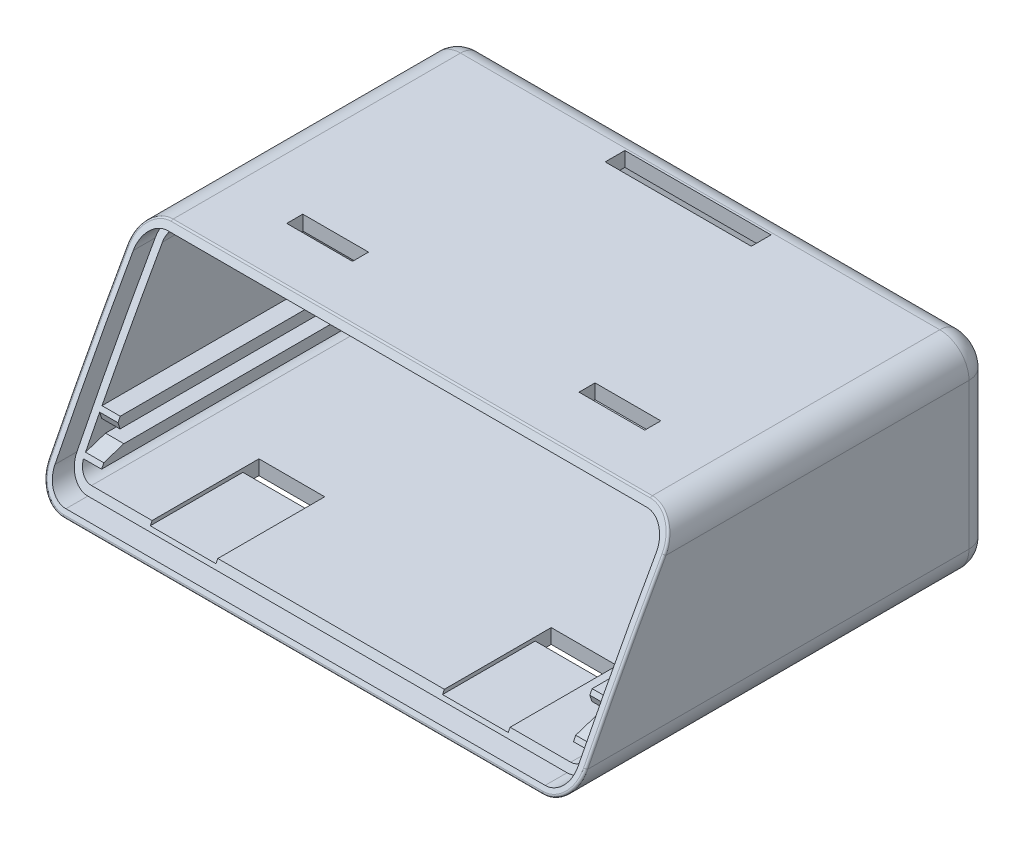
SolidWorks part; units mm, degrees
ref_plane "Front Plane" through (0, 0, 0) normal (0, 0, 1) x (1, 0, 0)
ref_plane "Top Plane" through (0, 0, 0) normal (0, 1, 0) x (1, 0, 0)
ref_plane "Right Plane" through (0, 0, 0) normal (1, 0, 0) x (0, 0, -1)
sketch "Sketch1" plane through (0, 0, 0) normal (0, 1, 0) x (1, 0, 0)
  line L1 (-36.79, -28.75) -> (36.79, -28.75)
  line L2 (-36.79, -28.75) -> (-36.79, 28.75)
  line L3 (-36.79, 28.75) -> (36.79, 28.75)
  line L4 (36.79, -28.75) -> (36.79, 28.75)
  line L5 (-36.79, -28.75) -> (36.79, 28.75) construction
  line L6 (-36.79, 28.75) -> (36.79, -28.75) construction
  point P0 (0, 0)
  dimension "D1" = 57.5
  dimension "D2" = 73.58
extrude "Boss-Extrude1" add sketch "Sketch1" along normal blind 28
fillet "Fillet1" radius 4 4 edges at (36.79, 28, 0) (36.79, 0, 0) (-36.79, 0, 0) (-36.79, 28, 0)
shell "Shell1" thickness 2
sketch "Sketch2" plane through (-36.79, 0, 0) normal (-1, 0, 0) x (0, 0, 1)
  line L0 (-28.75, 28) -> (28.75, 28) construction
  line L1 (13.75, 28) -> (28.75, 28)
  line L2 (28.75, 28) -> (28.75, 0)
  arc A0 (28.75, 0) -> (13.75, 28) centre (-397.2189, -210.1797) ccw
  dimension "D1" = 15
  dimension "D2" = 475
extrude "Cut-Extrude1" cut sketch "Sketch2" against normal through all
sketch "Sketch3" plane through (0, 0, -28.75) normal (0, 0, -1) x (-1, 0, 0)
  line L0 (-7.15, 18.7) -> (7.15, 18.7)
  line L1 (-6.95, 18.5) -> (6.95, 18.5) construction
  line L2 (-6.95, 18.5) -> (-6.95, 2.2) construction
  line L3 (-6.95, 2.2) -> (6.95, 2.2) construction
  line L4 (6.95, 18.5) -> (6.95, 2.2) construction
  line L5 (7.15, 18.7) -> (7.15, 2)
  line L6 (-7.15, 2) -> (7.15, 2)
  line L7 (-7.15, 18.7) -> (-7.15, 2)
  line L8 (27.25, 17.2) -> (38.3, 17.2)
  line L9 (27.45, 17) -> (38.1, 17) construction
  line L10 (27.45, 17) -> (27.45, 3.35) construction
  line L11 (27.45, 3.35) -> (38.1, 3.35) construction
  line L12 (38.1, 17) -> (38.1, 3.35) construction
  line L13 (38.3, 17.2) -> (38.3, 3.15)
  line L14 (27.25, 3.15) -> (38.3, 3.15)
  line L15 (27.25, 17.2) -> (27.25, 3.15)
  dimension "D1" = 0.2
  dimension "D2" = 0.2
fillet "Fillet2" radius 3 8 edges at (35.6184, 26.8284, -28.75) (36.79, 14, -28.75) (35.6184, 1.1716, -28.75) (0, 0, -28.75) (-35.6184, 1.1716, -28.75) (-36.79, 14, -28.75) (-35.6184, 26.8284, -28.75) (0, 28, -28.75)
sketch "Sketch4" plane through (0, 0, -26.75) normal (0, 0, 1) x (1, 0, 0)
  line L0 (32.79, 27) -> (-32.79, 27)
  line L1 (-35.79, 24) -> (-35.79, 4)
  line L2 (-32.79, 1) -> (32.79, 1)
  line L3 (35.79, 4) -> (35.79, 24)
  line L4 (32.79, 26) -> (-32.79, 26)
  line L5 (-34.79, 24) -> (-34.79, 4)
  line L6 (-32.79, 2) -> (32.79, 2)
  line L7 (34.79, 4) -> (34.79, 24)
  line L8 (32.79, 26) -> (-32.79, 26)
  line L9 (-34.79, 24) -> (-34.79, 4)
  line L10 (-32.79, 2) -> (32.79, 2)
  line L11 (34.79, 4) -> (34.79, 24)
  arc A0 (-32.79, 27) -> (-35.79, 24) centre (-32.79, 24) ccw
  arc A1 (-35.79, 4) -> (-32.79, 1) centre (-32.79, 4) ccw
  arc A2 (32.79, 1) -> (35.79, 4) centre (32.79, 4) ccw
  arc A3 (35.79, 24) -> (32.79, 27) centre (32.79, 24) ccw
  arc A4 (-32.79, 26) -> (-34.79, 24) centre (-32.79, 24) ccw
  arc A5 (-34.79, 4) -> (-32.79, 2) centre (-32.79, 4) ccw
  arc A6 (32.79, 2) -> (34.79, 4) centre (32.79, 4) ccw
  arc A7 (34.79, 24) -> (32.79, 26) centre (32.79, 24) ccw
  arc A8 (-32.79, 26) -> (-34.79, 24) centre (-32.79, 24) ccw
  arc A9 (-34.79, 4) -> (-32.79, 2) centre (-32.79, 4) ccw
  arc A10 (32.79, 2) -> (34.79, 4) centre (32.79, 4) ccw
  arc A11 (34.79, 24) -> (32.79, 26) centre (32.79, 24) ccw
  dimension "D1" = 0
  dimension "D2" = 1
extrude "Cut-Extrude3" cut sketch "Sketch4" against normal offset from surface (29.4971 mm away) 3 from offset 80
fillet "Fillet3" radius 0.3 8 edges at (35.4342, 27.0013, 14.3272) (36.79, 14.064, 21.517) (35.0952, 0.7311, 28.3885) (0, 0, 28.75) (-35.7081, 1.2642, 28.1239) (-36.79, 14.064, 21.517) (-35.0392, 27.3077, 14.1504) (0, 28, 13.75)
sketch "Sketch5" plane through (0, 0, -26.75) normal (0, 0, 1) x (1, 0, 0)
  line L1 (34.79, 5.25) -> (32.29, 5.25)
  line L2 (34.79, 5.25) -> (34.79, 3.75)
  line L3 (34.79, 3.75) -> (32.29, 3.75)
  line L4 (32.29, 5.25) -> (32.29, 3.75)
  line L5 (34.79, 7.05) -> (40.64, 7.05) construction
  line L6 (34.79, 7.25) -> (32.29, 7.25)
  line L7 (34.79, 7.25) -> (34.79, 8.75)
  line L8 (34.79, 8.75) -> (32.29, 8.75)
  line L9 (32.29, 7.25) -> (32.29, 8.75)
  line L10 (-40.64, 7.05) -> (40.64, 7.05) construction
  line L11 (40.64, 5.45) -> (34.79, 5.45) construction
  line L12 (-40.64, 5.45) -> (40.64, 5.45) construction
  line L14 (-34.79, 8.75) -> (-32.29, 8.75)
  line L15 (-34.79, 8.75) -> (-34.79, 7.25)
  line L16 (-34.79, 7.25) -> (-32.29, 7.25)
  line L17 (-32.29, 8.75) -> (-32.29, 7.25)
  line L18 (-34.79, 24) -> (-34.79, 4) construction
  line L19 (-34.79, 5.25) -> (-32.29, 5.25)
  line L20 (-34.79, 5.25) -> (-34.79, 3.75)
  line L21 (-34.79, 3.75) -> (-32.29, 3.75)
  line L22 (-32.29, 5.25) -> (-32.29, 3.75)
  line L23 (34.79, 24) -> (34.79, 4) construction
  dimension "D1" = 0.2
  dimension "D2" = 0.2
  dimension "D3" = 1.5
  dimension "D4" = 2.5
extrude "Boss-Extrude2" add sketch "Sketch5" along normal up to surface (49.8691 mm away)
sketch "Sketch6" plane through (0, 0, -28.75) normal (0, 0, -1) x (-1, 0, 0)
  line L0 (-7.15, 18.7) -> (7.15, 18.7)
  line L1 (-6.95, 18.5) -> (6.95, 18.5) construction
  line L2 (-6.95, 18.5) -> (-6.95, 2.2) construction
  line L3 (-6.95, 2.2) -> (6.95, 2.2) construction
  line L4 (6.95, 18.5) -> (6.95, 2.2) construction
  line L5 (7.15, 18.7) -> (7.15, 2)
  line L6 (-7.15, 2) -> (7.15, 2)
  line L7 (-7.15, 18.7) -> (-7.15, 2)
  line L8 (20.9, 17.2) -> (31.95, 17.2)
  line L9 (21.1, 17) -> (31.75, 17) construction
  line L10 (21.1, 17) -> (21.1, 3.35) construction
  line L11 (21.1, 3.35) -> (31.75, 3.35) construction
  line L12 (31.75, 17) -> (31.75, 3.35) construction
  line L13 (31.95, 17.2) -> (31.95, 3.15)
  line L14 (20.9, 3.15) -> (31.95, 3.15)
  line L15 (20.9, 17.2) -> (20.9, 3.15)
  dimension "D1" = 0.2
  dimension "D2" = 0.2
extrude "Cut-Extrude4" cut sketch "Sketch6" against normal up to surface (2 mm away) up to face at (0, 9.2763, -26.75)
sketch "Sketch7" plane through (0, 28, 0) normal (0, 1, 0) x (1, 0, 0)
  line L0 (0, 0) -> (0, 25.75) construction
  line L1 (-24.5, -4.13) -> (-24.5, -6.33)
  line L2 (16.5, -6.13) -> (23.5, -6.13) construction
  line L3 (16.5, -6.13) -> (16.5, -4.33) construction
  line L4 (16.5, -4.33) -> (23.5, -4.33) construction
  line L5 (23.5, -6.13) -> (23.5, -4.33) construction
  line L6 (15.5, -4.13) -> (24.5, -4.13)
  line L7 (15.5, -4.13) -> (15.5, -6.33)
  line L8 (15.5, -6.33) -> (24.5, -6.33)
  line L9 (32.79, 25.75) -> (-32.79, 25.75) construction
  line L10 (-15.5, -6.33) -> (-24.5, -6.33)
  line L11 (-15.5, -4.13) -> (-15.5, -6.33)
  line L12 (-15.5, -4.13) -> (-24.5, -4.13)
  line L13 (-23.5, -6.13) -> (-23.5, -4.33) construction
  line L14 (-16.5, -4.33) -> (-23.5, -4.33) construction
  line L15 (-16.5, -6.13) -> (-16.5, -4.33) construction
  line L16 (-16.5, -6.13) -> (-23.5, -6.13) construction
  line L18 (24.5, -4.13) -> (24.5, -6.33)
  dimension "D1" = 0.2
  dimension "D2" = 0.2
  dimension "D3" = 1
  dimension "D4" = 1
extrude "Cut-Extrude5" cut sketch "Sketch7" against normal up to surface (2 mm away) up to face at (0, 26, -7.4237)
sketch "Sketch11" plane through (0, 0, 0) normal (0, -1, 0) x (1, 0, 0)
  line L0 (0, 0) -> (0, 28.5672) construction
  line L1 (-23.5, 10.33) -> (-16.5, 10.33) construction
  line L2 (-23.5, 10.33) -> (-23.5, 12.13) construction
  line L3 (-23.5, 12.13) -> (-16.5, 12.13) construction
  line L4 (-16.5, 10.33) -> (-16.5, 12.13) construction
  line L5 (-24.5, 12.33) -> (-15.5, 12.33)
  line L6 (-24.5, 12.33) -> (-24.5, 10.13)
  line L7 (-24.5, 10.13) -> (-15.5, 10.13)
  line L8 (-15.5, 12.33) -> (-15.5, 10.13)
  line L9 (32.79, 28.5672) -> (-32.79, 28.5672) construction
  line L10 (16.5, 10.33) -> (16.5, 12.13) construction
  line L11 (23.5, 12.13) -> (16.5, 12.13) construction
  line L12 (23.5, 10.33) -> (23.5, 12.13) construction
  line L13 (23.5, 10.33) -> (16.5, 10.33) construction
  line L14 (15.5, 12.33) -> (15.5, 10.13)
  line L15 (24.5, 10.13) -> (15.5, 10.13)
  line L16 (24.5, 12.33) -> (24.5, 10.13)
  line L17 (24.5, 12.33) -> (15.5, 12.33)
  dimension "D1" = 0.2
  dimension "D2" = 0.2
  dimension "D3" = 1
  dimension "D4" = 1
extrude "Cut-Extrude8" cut sketch "Sketch11" against normal up to surface (2 mm away) up to face at (3.205, 2, -14.1017)
sketch "Sketch8" plane through (0, 28, 0) normal (0, 1, 0) x (1, 0, 0)
  line L0 (-32.79, 28.75) -> (32.79, 28.75) construction
  line L1 (-10, 25.15) -> (10, 25.15)
  line L2 (-10, 25.15) -> (-10, 22.75)
  line L3 (-10, 22.75) -> (10, 22.75)
  line L4 (10, 25.15) -> (10, 22.75)
  line L5 (0, 0) -> (0, 22.75) construction
  dimension "D1" = 3.6
  dimension "D2" = 2.4
  dimension "D3" = 20
extrude "Cut-Extrude6" cut sketch "Sketch8" against normal up to surface (2 mm away) up to face at (-20, 26, 5.23)
sketch "Sketch9" plane through (0, 0, 12.33) normal (0, 0, -1) x (-1, 0, 0)
  line L2 (-32.79, 2) -> (-7.15, 2) construction
  line L4 (-24.5, 2) -> (-24.5, 0) construction
  line L5 (24.5, 2) -> (24.5, 0) construction
  line L6 (15.5, 2) -> (15.5, 0) construction
  line L7 (15.5, 2) -> (24.5, 2) construction
  line L14 (-15.5, 26) -> (-15.5, 28) construction
  line L22 (24.5, 1.5) -> (15.5, 1.5)
  line L24 (-24.5, 2) -> (-24.5, 1.5)
  line L26 (-15.5, 1.5) -> (-15.5, 2)
  line L27 (-15.5, 2) -> (-24.5, 2)
  line L28 (15.5, 2) -> (15.5, 1.5)
  line L29 (-15.5, 1.5) -> (-24.5, 1.5)
  line L30 (24.5, 1.5) -> (24.5, 2)
  line L31 (24.5, 2) -> (15.5, 2)
  dimension "D3" = 0.5
extrude "Cut-Extrude7" cut sketch "Sketch9" against normal through all
sketch "Sketch10" plane through (0, 0, -26.75) normal (0, 0, 1) x (1, 0, 0)
  line L0 (-20.9, 17.2) -> (-20.9, 3.15) construction
  line L1 (-20.9, 7.05) -> (-7.15, 7.05)
  line L2 (-20.9, 7.05) -> (-20.9, 5.45)
  line L3 (-20.9, 5.45) -> (-7.15, 5.45)
  line L4 (-7.15, 7.05) -> (-7.15, 5.45)
  line L5 (-7.15, 2) -> (-7.15, 18.7) construction
  line L6 (34.79, 7.25) -> (34.79, 5.25) construction
  line L7 (34.79, 5.25) -> (7.15, 5.25)
  line L8 (34.79, 5.25) -> (34.79, 7.25)
  line L9 (34.79, 7.25) -> (7.15, 7.25)
  line L10 (7.15, 5.25) -> (7.15, 7.25)
  line L11 (32.29, 5.25) -> (34.79, 5.25) construction
  line L12 (7.15, 18.7) -> (7.15, 2) construction
  line L13 (34.79, 7.25) -> (32.29, 7.25) construction
  line L14 (-31.95, 3.15) -> (-31.95, 17.2) construction
  line L15 (-34.79, 7.25) -> (-31.95, 7.25)
  line L16 (-34.79, 7.25) -> (-34.79, 5.25)
  line L17 (-34.79, 5.25) -> (-31.95, 5.25)
  line L18 (-31.95, 7.25) -> (-31.95, 5.25)
  line L19 (-34.79, 5.25) -> (-32.29, 5.25) construction
sketch "Sketch12" plane through (0, 0, 6.33) normal (0, 0, -1) x (-1, 0, 0)
  line L0 (24.5, 26.5) -> (15.5, 26.5)
  line L2 (-15.5, 26.5) -> (-24.5, 26.5)
  line L4 (24.5, 26) -> (24.5, 28)
  line L5 (24.5, 28) -> (15.5, 28)
  line L6 (15.5, 28) -> (15.5, 26)
  line L7 (15.5, 26) -> (24.5, 26)
  line L8 (24.5, 26) -> (24.5, 26.5)
  line L10 (15.5, 26.5) -> (15.5, 26)
  line L11 (15.5, 26) -> (24.5, 26)
  line L12 (-15.5, 26) -> (-15.5, 28)
  line L13 (-15.5, 28) -> (-24.5, 28)
  line L14 (-24.5, 28) -> (-24.5, 26)
  line L15 (-24.5, 26) -> (-15.5, 26)
  line L16 (-15.5, 26) -> (-15.5, 26.5)
  line L18 (-24.5, 26.5) -> (-24.5, 26)
  line L19 (-24.5, 26) -> (-15.5, 26)
  dimension "D3" = 0.5
  dimension "D4" = 0.5
  dimension "D1" = 0
  dimension "D2" = 0
extrude "Cut-Extrude9" cut sketch "Sketch12" against normal through all
extrude "Boss-Extrude3" add sketch "Sketch10" along normal blind 0.5
chamfer "Chamfer1" distance 1 angle 45 4 edges at (33.54, 5.25, 23.1191) (33.54, 7.25, 22.0954) (-33.54, 7.25, 22.0954) (-33.54, 5.25, 23.1191)
sketch "Sketch13" plane through (0, 0, -25.15) normal (0, 0, 1) x (1, 0, 0)
  line L4 (10, 26) -> (10, 28)
  line L5 (10, 28) -> (-10, 28)
  line L6 (-10, 28) -> (-10, 26)
  line L7 (-10, 26) -> (10, 26)
  line L8 (10, 26) -> (10, 28)
  line L9 (10, 28) -> (-10, 28)
  line L10 (-10, 28) -> (-10, 26)
  line L11 (-10, 26) -> (10, 26)
  dimension "D1" = 0
extrude "Cut-Extrude10" cut sketch "Sketch13" against normal blind 0.3
